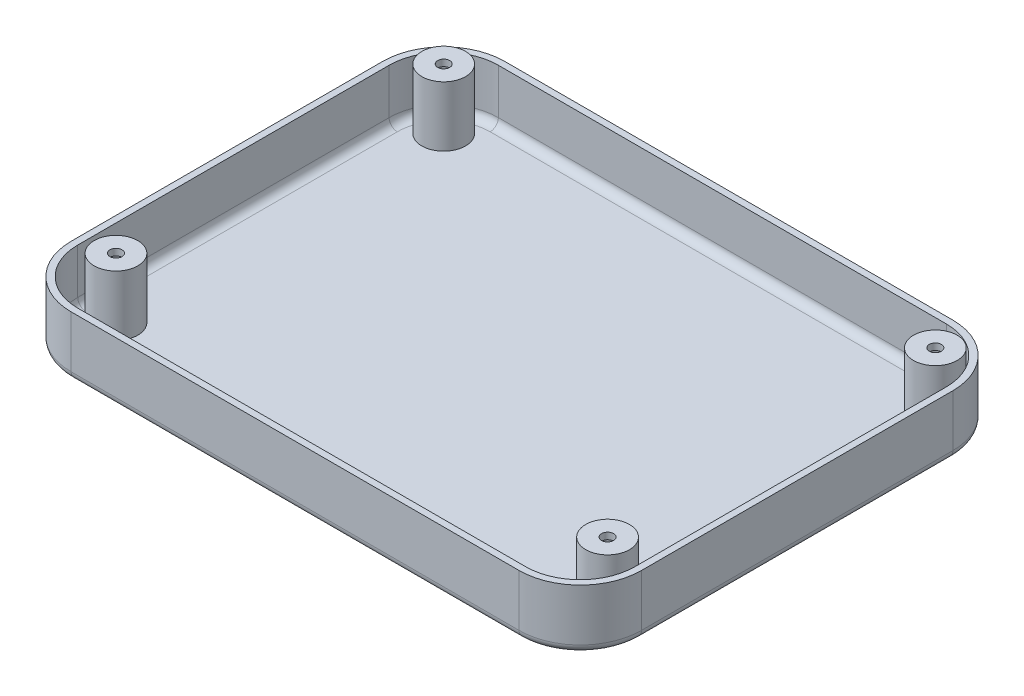
SolidWorks part; units mm, degrees
ref_plane "前视基准面" through (0, 0, 0) normal (0, 0, 1) x (1, 0, 0)
ref_plane "上视基准面" through (0, 0, 0) normal (0, 1, 0) x (1, 0, 0)
ref_plane "右视基准面" through (0, 0, 0) normal (1, 0, 0) x (0, 0, -1)
sketch "草图1" plane through (0, 0, 0) normal (0, 1, 0) x (1, 0, 0)
  line L0 (0, 0) -> (0, 14.1394) construction
  line L2 (51, -26) -> (51, 26)
  line L3 (41, 36) -> (-41, 36)
  line L4 (-51, -26) -> (-51, 26)
  line L5 (51, -36) -> (-51, 36) construction
  line L6 (51, 36) -> (-51, -36) construction
  line L8 (0, 0) -> (16.0162, 0) construction
  line L9 (51, -26) -> (51, -31)
  line L11 (51, -31) -> (51, -41) construction
  line L12 (51, -41) -> (41, -41) construction
  line L13 (41, -41) -> (-41, -41)
  line L14 (-51, -26) -> (-51, -31)
  arc A0 (41, 36) -> (51, 26) centre (41, 26) cw
  arc A1 (-41, 36) -> (-51, 26) centre (-41, 26) ccw
  arc A4 (41, -41) -> (51, -31) centre (41, -31) ccw
  arc A5 (-41, -41) -> (-51, -31) centre (-41, -31) cw
  point P0 (0, 0)
  point P6 (0, 0)
extrude "凸台-拉伸3" add sketch "草图1" along normal blind 1.2
sketch "草图4" plane through (0, 0, 0) normal (0, 1, 0) x (1, 0, 0)
  line L0 (0, 0) -> (0, 14.1394) construction
  line L2 (51, -26) -> (51, 26)
  line L3 (41, 36) -> (-41, 36)
  line L4 (-51, -26) -> (-51, 26)
  line L5 (51, -36) -> (-51, 36) construction
  line L6 (51, 36) -> (-51, -36) construction
  line L8 (0, 0) -> (16.0162, 0) construction
  line L9 (-41, 37.2) -> (41, 37.2)
  line L11 (52.2, 26) -> (52.2, -26)
  line L13 (-52.2, -26) -> (-52.2, 26)
  line L14 (-51, -26) -> (-51, -31)
  line L15 (-51, 26) -> (-51, -31) construction
  line L16 (-52.2, -26) -> (-52.2, -31)
  line L17 (52.2, -26) -> (52.2, -31)
  line L18 (51, -26) -> (51, -31)
  line L19 (-41.0001, -40.9999) -> (41.0001, -40.9999)
  line L20 (41.0001, -42.1999) -> (-41.0001, -42.1999)
  arc A0 (41, 36) -> (51, 26) centre (41, 26) cw
  arc A1 (-41, 36) -> (-51, 26) centre (-41, 26) ccw
  arc A4 (-41, 37.2) -> (-52.2, 26) centre (-41, 26) ccw
  arc A5 (41, 37.2) -> (52.2, 26) centre (41, 26) cw
  arc A8 (-51, -31) -> (-41.0001, -40.9999) centre (-41.0001, -31) ccw
  arc A9 (-52.2, -31) -> (-41.0001, -42.1999) centre (-41.0001, -31) ccw
  arc A10 (51, -31) -> (41.0001, -40.9999) centre (41.0001, -31) cw
  arc A11 (52.2, -31) -> (41.0001, -42.1999) centre (41.0001, -31) cw
  point P0 (0, 0)
  point P6 (0, 0)
extrude "凸台-拉伸4" add sketch "草图4" along normal blind 11
sketch "草图6" plane through (0, 1.2, 0) normal (0, 1, 0) x (1, 0, 0)
  line L0 (0, 0) -> (0, 20.4299) construction
  line L1 (0, 0) -> (-19.2721, 0) construction
  circle A0 centre (-45, 30) radius 4
  circle A1 centre (-45, 30) radius 2.4
  circle A2 centre (45, 30) radius 2.4
  circle A3 centre (45, 30) radius 4
  circle A4 centre (45, -30) radius 4
  circle A5 centre (45, -30) radius 2.4
  circle A6 centre (-45, -30) radius 2.4
  circle A7 centre (-45, -30) radius 4
extrude "凸台-拉伸5" add sketch "草图6" along normal blind 11
sketch "草图7" plane through (0, 1.2, 0) normal (0, 1, 0) x (1, 0, 0)
  circle A0 centre (-45, 30) radius 2.4
  circle A1 centre (45, 30) radius 1.7
  circle A2 centre (45, -30) radius 1.7
  circle A3 centre (-45, -30) radius 2.4
extrude "切除-拉伸1" cut sketch "草图7" against normal blind 10
sketch "草图8" plane through (0, 12.2, 0) normal (0, 1, 0) x (1, 0, 0)
  line L0 (0, 0) -> (0, 9.5638) construction
  line L1 (0, 0) -> (10.7565, 0) construction
  circle A0 centre (-45, 30) radius 2.4
  circle A1 centre (-45, 30) radius 1.1
  circle A2 centre (45, 30) radius 2.4
  circle A3 centre (45, 30) radius 1.1
  circle A4 centre (45, -30) radius 1.1
  circle A5 centre (45, -30) radius 2.4
  circle A6 centre (-45, -30) radius 1.1
  circle A7 centre (-45, -30) radius 2.4
extrude "凸台-拉伸6" add sketch "草图8" against normal blind 1.2
fillet "圆角1" radius 1.5 16 edges at (0, 0, -37.2) (48.9196, 0, -33.9196) (52.2, 0, 2.5) (48.9196, 0, 38.9195) (0, 0, 42.1999) (-48.9196, 0, 38.9195) (-52.2, 0, 2.5) (48.0711, 1.2, -33.0711) (51, 1.2, 2.5) (48.0711, 1.2, 38.071) (0, 1.2, 40.9999) (-48.0711, 1.2, 38.071) (-51, 1.2, 2.5) (-48.0711, 1.2, -33.0711) (-48.9196, 0, -33.9196) (0, 1.2, -36)
